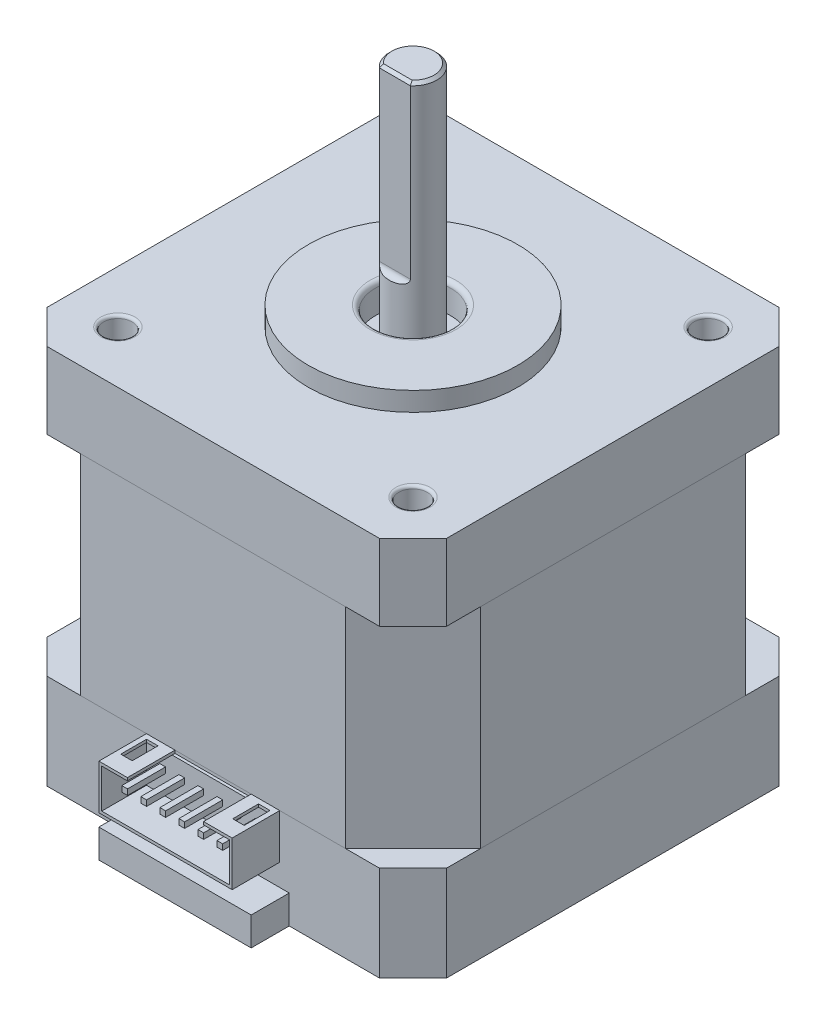
SolidWorks part; units mm, degrees
ref_plane "Front Plane" through (0, 0, 0) normal (0, 0, 1) x (1, 0, 0)
ref_plane "Top Plane" through (0, 0, 0) normal (0, 1, 0) x (1, 0, 0)
ref_plane "Right Plane" through (0, 0, 0) normal (1, 0, 0) x (0, 0, -1)
sketch "Sketch1" plane through (0, 0, 0) normal (0, 1, 0) x (1, 0, 0)
  line L0 (-21, 17.4645) -> (-17.4645, 21)
  line L1 (17.4645, -21) -> (-17.4645, -21)
  line L2 (21, -17.4645) -> (21, 17.4645)
  line L3 (17.4645, 21) -> (-17.4645, 21)
  line L4 (-21, -17.4645) -> (-21, 17.4645)
  line L6 (19.2322, 19.2322) -> (-19.2322, -19.2322) construction
  line L7 (17.4645, -21) -> (21, -17.4645)
  line L8 (-21, 0) -> (21, 0) construction
  line L9 (17.4645, 21) -> (21, 17.4645)
  line L10 (-21, -17.4645) -> (-17.4645, -21)
  point P0 (0, 0)
  point P4 (0, 21)
  dimension "D1" = 42
  dimension "D2" = 42
  dimension "D3" = 5
  dimension "D4" = 45
extrude "bottom" add sketch "Sketch1" along normal blind 10
sketch "Sketch2" plane through (0, 10, 0) normal (0, 1, 0) x (1, 0, 0)
  line L4 (-21, 0) -> (21, 0) construction
  line L5 (-21, 17.4645) -> (-21, -17.4645) construction
  line L6 (21, -17.4645) -> (21, 17.4645) construction
  line L7 (0, 21) -> (0, -21) construction
  line L8 (17.4645, 21) -> (-17.4645, 21) construction
  line L9 (-17.4645, -21) -> (17.4645, -21) construction
  line L10 (-21, 13.9289) -> (-13.9289, 21)
  line L11 (21, 13.9289) -> (13.9289, 21)
  line L16 (-21, -13.9289) -> (-13.9289, -21)
  line L17 (21, -13.9289) -> (13.9289, -21)
  line L18 (-13.9289, 21) -> (13.9289, 21)
  line L19 (21, 13.9289) -> (21, -13.9289)
  line L20 (13.9289, -21) -> (-13.9289, -21)
  line L22 (-21, -13.9289) -> (-21, 13.9289)
  dimension "D1" = 45
  dimension "D2" = 10
extrude "middle" add sketch "Sketch2" along normal blind 22 separate body
sketch "Sketch3" plane through (0, 32, 0) normal (0, 1, 0) x (1, 0, 0)
  line L32 (-21, 17.4645) -> (-21, -17.4645)
  line L33 (-17.4645, 21) -> (-21, 17.4645)
  line L34 (17.4645, 21) -> (-17.4645, 21)
  line L35 (21, 17.4645) -> (17.4645, 21)
  line L36 (21, -17.4645) -> (21, 17.4645)
  line L37 (17.4645, -21) -> (21, -17.4645)
  line L38 (-17.4645, -21) -> (17.4645, -21)
  line L39 (-21, -17.4645) -> (-17.4645, -21)
  line L40 (-21, 17.4645) -> (-21, -17.4645)
  line L41 (-17.4645, 21) -> (-21, 17.4645)
  line L42 (17.4645, 21) -> (-17.4645, 21)
  line L43 (21, 17.4645) -> (17.4645, 21)
  line L44 (21, -17.4645) -> (21, 17.4645)
  line L45 (17.4645, -21) -> (21, -17.4645)
  line L46 (-17.4645, -21) -> (17.4645, -21)
  line L47 (-21, -17.4645) -> (-17.4645, -21)
  dimension "D1" = 0
extrude "top" add sketch "Sketch3" along normal blind 10 separate body
sketch "Sketch4" plane through (0, 0, 21) normal (0, 0, 1) x (1, 0, 0)
  line L0 (-17.4645, 0) -> (17.4645, 0) construction
  line L1 (-8, 0) -> (8, 0)
  line L2 (-8, 0) -> (-8, 3)
  line L3 (-8, 3) -> (8, 3)
  line L4 (8, 0) -> (8, 3)
  point P6 (0, 3)
  dimension "D1" = 16
  dimension "D2" = 3
extrude "JST_extension" add sketch "Sketch4" along normal blind 4
sketch "Sketch5" plane through (0, 42, 0) normal (0, 1, 0) x (1, 0, 0)
  circle A0 centre (0, 0) radius 11
  dimension "D1" = 22
extrude "top trim" cut sketch "Sketch5" against normal blind 2 flip side to cut
sketch "Sketch9" plane through (0, 40, 0) normal (0, 1, 0) x (1, 0, 0)
  line L0 (0, 21) -> (0, 0) construction
  line L1 (17.4645, 21) -> (-17.4645, 21) construction
  line L2 (0, 0) -> (21, 0) construction
  line L3 (21, -17.4645) -> (21, 17.4645) construction
  circle A0 centre (-15.5, 15.5) radius 1.5
  circle A1 centre (15.5, 15.5) radius 1.5
  circle A2 centre (-15.5, -15.5) radius 1.5
  circle A3 centre (15.5, -15.5) radius 1.5
  dimension "D3" = 3
  dimension "D1" = 31
  dimension "D2" = 31
extrude "mount" cut sketch "Sketch9" against normal blind 5
sketch "Sketch6" plane through (0, 42, 0) normal (0, 1, 0) x (1, 0, 0)
  circle A0 centre (0, 0) radius 4
  dimension "D1" = 8
extrude "shaft_recess" cut sketch "Sketch6" against normal blind 3
sketch "Sketch7" plane through (0, 39, 0) normal (0, 1, 0) x (1, 0, 0)
  circle A0 centre (0, 0) radius 2.5
  dimension "D1" = 5
extrude "shaft" add sketch "Sketch7" along normal blind 25 separate body
sketch "Sketch8" plane through (0, 64, 0) normal (0, 1, 0) x (1, 0, 0)
  line L0 (-1.6248, -1.9) -> (1.6248, -1.9)
  circle A0 centre (0, 0) radius 2.5 construction
  arc A1 (-1.6248, -1.9) -> (1.6248, -1.9) centre (0, 0) ccw
  point P5 (0, -2.5)
  dimension "D1" = 0.6
extrude "D_shaft_trim" cut sketch "Sketch8" against normal blind 18.5
chamfer "shaft_top_chamfer" distance 0.3 angle 45 2 edges at (0, 64, -2.5) (0, 64, 1.9)
sketch "Sketch10" plane through (0, 0, 21) normal (0, 0, 1) x (1, 0, 0)
  line L0 (-13.9289, 10) -> (13.9289, 10) construction
  line L1 (7, 5.3) -> (-7, 5.3)
  line L2 (7, 5.3) -> (7, 10)
  line L3 (7, 10) -> (-7, 10)
  line L4 (-7, 5.3) -> (-7, 10)
  line L5 (7, 5.3) -> (-7, 10) construction
  line L6 (7, 10) -> (-7, 5.3) construction
  point P0 (0, 7.65)
  dimension "D1" = 4.7
  dimension "D2" = 14
extrude "JST" add sketch "Sketch10" along normal blind 5 separate body
shell "JST_shell" thickness 0.3 removed face at (0, 7.65, 26)
sketch "Sketch11" plane through (0, 10, 0) normal (0, 1, 0) x (1, 0, 0)
  line L0 (-17.4645, -21) -> (17.4645, -21) construction
  line L1 (4, -26.2916) -> (-4, -26.2916)
  line L2 (4, -26.2916) -> (4, -21)
  line L3 (4, -21) -> (-4, -21)
  line L4 (-4, -26.2916) -> (-4, -21)
  line L5 (4, -26.2916) -> (-4, -21) construction
  line L6 (4, -21) -> (-4, -26.2916) construction
  line L8 (6.4842, -21.5035) -> (5.2791, -21.5035)
  line L9 (6.4842, -21.5035) -> (6.4842, -24.2184)
  line L10 (6.4842, -24.2184) -> (5.2791, -24.2184)
  line L11 (5.2791, -21.5035) -> (5.2791, -24.2184)
  line L12 (0, -25.85) -> (0, 25.85) construction
  line L13 (-6.4842, -24.2184) -> (-5.2791, -24.2184)
  line L14 (-5.2791, -21.5035) -> (-5.2791, -24.2184)
  line L15 (-6.4842, -21.5035) -> (-5.2791, -21.5035)
  line L16 (-6.4842, -21.5035) -> (-6.4842, -24.2184)
  point P0 (0, -23.6458)
  dimension "D1" = 8
extrude "JST_shaper" cut sketch "Sketch11" against normal up to surface (0.3 mm away) up to face at (0, 9.7, 23.65)
sketch "Sketch12" plane through (0, 0, 21.3) normal (0, 0, 1) x (1, 0, 0)
  line L0 (-3.29, 8.2775) -> (-3.29, 7.6775)
  line L1 (-5.29, 8.2775) -> (-4.69, 8.2775)
  line L2 (-5.29, 8.2775) -> (-5.29, 7.6775)
  line L3 (-5.29, 7.6775) -> (-4.69, 7.6775)
  line L4 (-4.69, 8.2775) -> (-4.69, 7.6775)
  line L5 (-5.29, 8.2775) -> (-4.69, 7.6775) construction
  line L6 (-5.29, 7.6775) -> (-4.69, 8.2775) construction
  line L7 (-3.29, 8.2775) -> (-2.69, 8.2775)
  line L8 (-2.69, 8.2775) -> (-2.69, 7.6775)
  line L9 (-3.29, 7.6775) -> (-2.69, 7.6775)
  line L10 (-1.29, 8.2775) -> (-1.29, 7.6775)
  line L11 (-1.29, 8.2775) -> (-0.69, 8.2775)
  line L12 (-0.69, 8.2775) -> (-0.69, 7.6775)
  line L13 (-1.29, 7.6775) -> (-0.69, 7.6775)
  line L14 (0.71, 8.2775) -> (0.71, 7.6775)
  line L15 (0.71, 8.2775) -> (1.31, 8.2775)
  line L16 (1.31, 8.2775) -> (1.31, 7.6775)
  line L17 (0.71, 7.6775) -> (1.31, 7.6775)
  line L18 (2.71, 8.2775) -> (2.71, 7.6775)
  line L19 (2.71, 8.2775) -> (3.31, 8.2775)
  line L20 (3.31, 8.2775) -> (3.31, 7.6775)
  line L21 (2.71, 7.6775) -> (3.31, 7.6775)
  line L22 (4.71, 8.2775) -> (4.71, 7.6775)
  line L23 (4.71, 8.2775) -> (5.31, 8.2775)
  line L24 (5.31, 8.2775) -> (5.31, 7.6775)
  line L25 (4.71, 7.6775) -> (5.31, 7.6775)
  line L28 (-6.7, 9.7) -> (-6.7, 5.6) construction
  point P0 (-4.99, 7.9775)
  dimension "D1" = 0.6
  dimension "D3" = 1.71
  dimension "D2" = 6
extrude "JST_pins" add sketch "Sketch12" along normal blind 4 separate body
fillet "Fillet2" radius 0.5 1 edges at (0, 42, 4)
fillet "Fillet3" radius 0.3 4 edges at (-15.5, 40, 14) (-15.5, 40, -14) (15.5, 40, -17) (15.5, 40, 17)
fillet "Fillet4" radius 0.6 1 edges at (0, 45.5, 1.9)
